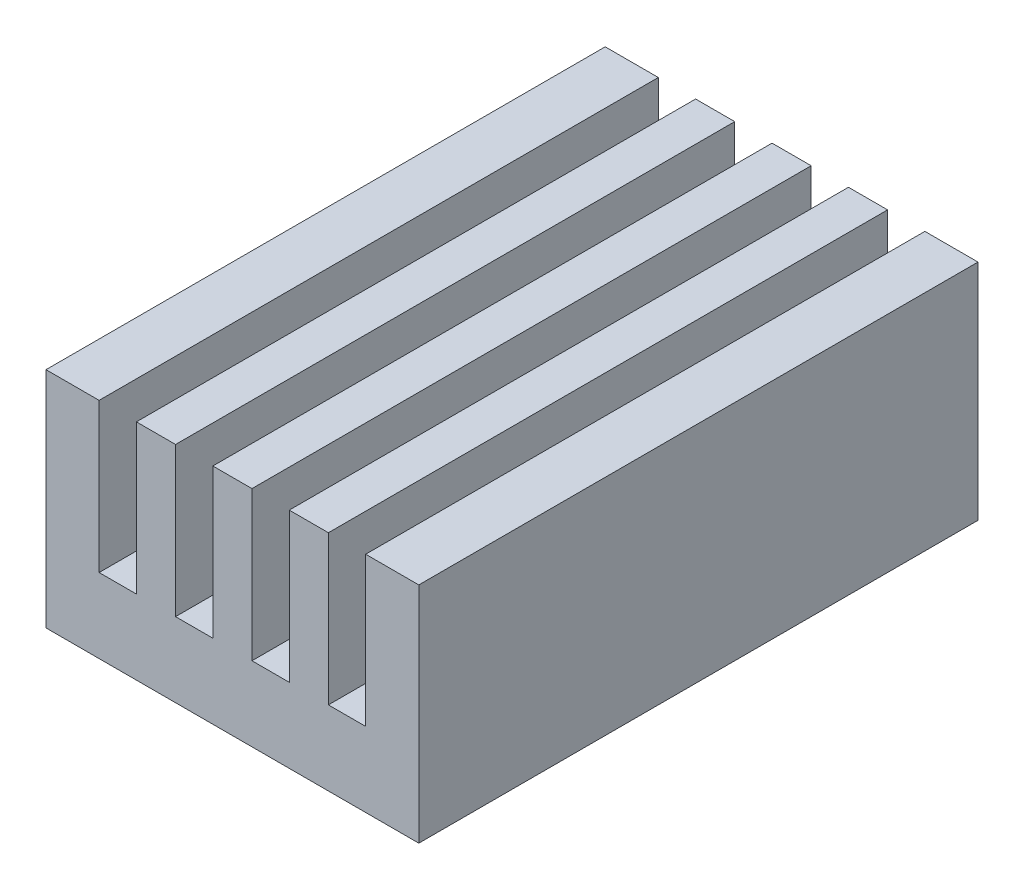
SolidWorks part; units mm, degrees
material "6061-T6 (SS)"
ref_plane "Front Plane" through (0, 0, 0) normal (0, 0, 1) x (1, 0, 0)
ref_plane "Top Plane" through (0, 0, 0) normal (0, 1, 0) x (1, 0, 0)
ref_plane "Right Plane" through (0, 0, 0) normal (1, 0, 0) x (0, 0, -1)
sketch "Sketch1" plane through (0, 0, 0) normal (0, 0, 1) x (1, 0, 0)
  line L0 (-5, 6) -> (-5, 0)
  line L1 (-5, 6) -> (5, 6)
  line L2 (-5, 0) -> (5, 0)
  line L3 (5, 6) -> (5, 0)
  line L4 (-5, 6) -> (5, 0) construction
  line L5 (-5, 0) -> (5, 6) construction
  line L8 (0, 6) -> (0, 0) construction
  line L9 (-0.525, 6) -> (-0.525, 2)
  line L10 (0.525, 6) -> (1.525, 6)
  line L11 (0.525, 6) -> (0.525, 2)
  line L12 (0.525, 2) -> (1.525, 2)
  line L13 (1.525, 6) -> (1.525, 2)
  line L14 (2.575, 6) -> (3.575, 6)
  line L15 (2.575, 6) -> (2.575, 2)
  line L16 (2.575, 2) -> (3.575, 2)
  line L17 (3.575, 6) -> (3.575, 2)
  line L18 (-0.525, 2) -> (-1.525, 2)
  line L19 (-1.525, 6) -> (-1.525, 2)
  line L20 (-2.575, 6) -> (-2.575, 2)
  line L21 (-2.575, 2) -> (-3.575, 2)
  line L22 (-3.575, 6) -> (-3.575, 2)
  point P1 (0, 3)
  point P3 (0, 0)
  dimension "D1" = 10
  dimension "D2" = 6
  dimension "D6" = 1
  dimension "D7" = 0.525
  dimension "D8" = 4
  dimension "D9" = 1.05
  dimension "D10" = 1
extrude "Boss-Extrude1" add sketch "Sketch1" along normal blind 15 contours L0 L2 L3 L1 L17 L16 L15 L13 L12 L11 L9 L18 L19 L20 L21 L22 region at (0, 2.6364, 0)
equation "\"D10@Sketch1\"=\"D6@Sketch1\""
